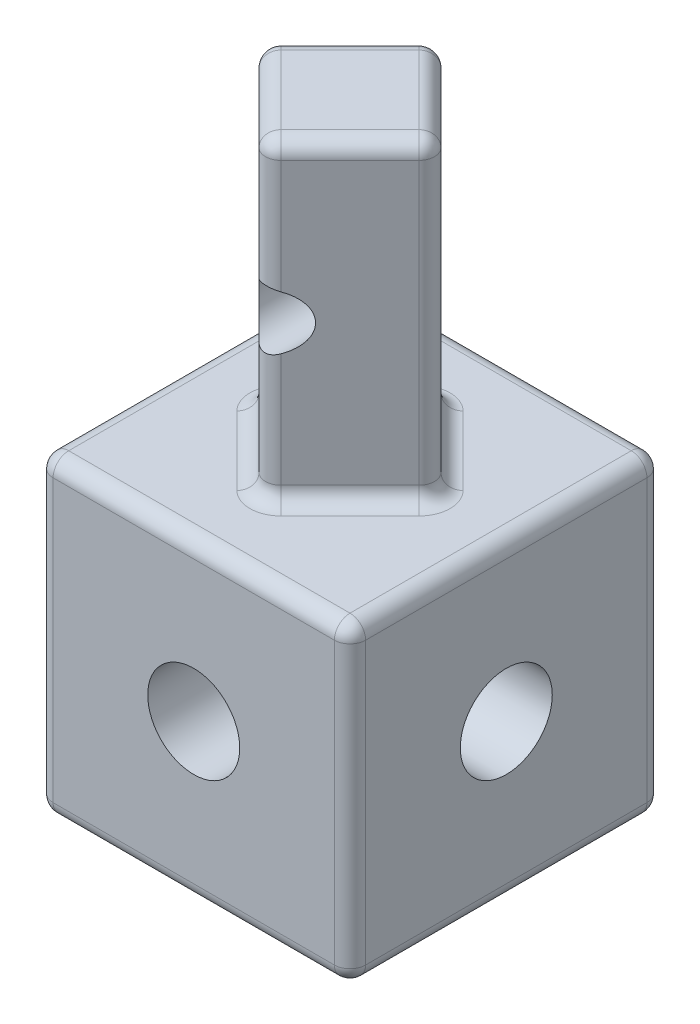
SolidWorks part; units mm, degrees
ref_plane "Front Plane" through (0, 0, 0) normal (0, 0, 1) x (1, 0, 0)
ref_plane "Top Plane" through (0, 0, 0) normal (0, 1, 0) x (1, 0, 0)
ref_plane "Right Plane" through (0, 0, 0) normal (1, 0, 0) x (0, 0, -1)
sketch "Sketch1" plane through (0, 0, 0) normal (0, 1, 0) x (1, 0, 0)
  line L1 (0, 0) -> (17, 0)
  line L2 (0, 0) -> (0, -17)
  line L3 (0, -17) -> (17, -17)
  line L4 (17, 0) -> (17, -17)
  dimension "D1" = 17
extrude "Boss-Extrude1" add sketch "Sketch1" along normal blind 17
sketch "Sketch2" plane through (0, 17, 0) normal (0, 1, 0) x (1, 0, 0)
  line L0 (0, 0) -> (17, -17) construction
  line L2 (3.5503, -8.5) -> (8.5, -3.5503)
  line L3 (3.5503, -8.5) -> (8.5, -13.4497)
  line L4 (8.5, -13.4497) -> (13.4497, -8.5)
  line L5 (8.5, -3.5503) -> (13.4497, -8.5)
  line L6 (3.5503, -8.5) -> (13.4497, -8.5) construction
  line L7 (8.5, -13.4497) -> (8.5, -3.5503) construction
  point P4 (8.5, -8.5)
  dimension "D1" = 7
  dimension "D2" = 90
extrude "Boss-Extrude2" add sketch "Sketch2" along normal blind 17
sketch3d "3DSketch7"
  line L0 (13.4497, 34, 8.5) -> (13.4497, 17, 8.5) construction
  circle A0 centre (8.4384, 25.4985, 8.5) radius 1.6
  point P4 (8.4384, 25.4985, 10.1)
  dimension "D1" = 3.2
extrude "Cut-Extrude1" cut sketch "3DSketch7" along direction (0, 0, 1) on the side of the normal through all and the other way blind 18 contours A0
hole_wizard "CBORE for #00 Binding Head Machine Screw1" positions "Sketch6" profile "Sketch8" counterbore size "#00" standard "ANSI Inch"
sketch "Sketch6" plane through (0, 0, 17) normal (0, 0, 1) x (1, 0, 0)
  point P0 (8.5, 8.5)
sketch "Sketch8" plane through (8.5, 8.5, 17) normal (1, 0, 0) x (0, -1, 0)
  line L0 (0, 0) -> (0, 10.9157)
  line L1 (0, 10.9157) -> (1.524, 10)
  line L2 (1.524, 10) -> (1.524, 5.4004)
  line L3 (1.524, 5.4004) -> (2.159, 4.0386)
  line L4 (2.159, 4.0386) -> (2.5019, 4.0386)
  line L5 (2.5019, 4.0386) -> (2.5019, 0)
  line L6 (2.5019, 0) -> (0, 0)
  line L9 (-1.524, 5.4004) -> (-2.159, 4.0386) construction
  line L10 (0, 10.9157) -> (-1.524, 10) construction
  line L11 (0, -6.35) -> (0, 107.95) construction
  dimension "Hole Dia." = 3.048
  dimension "Hole Depth" = 10
  dimension "C'Bore Dia." = 5.0038
  dimension "C'Bore Depth" = 4.0386
  dimension "Mid C'Sink Dia." = 4.318
  dimension "Mid C'Sink Angle" = 50
  dimension "Drill Angle" = 118
hole_wizard "CBORE for #00 Binding Head Machine Screw2" positions "Sketch9" profile "Sketch10" counterbore size "#00" standard "ANSI Inch"
sketch "Sketch9" plane through (17, 0, 0) normal (1, 0, 0) x (0, 0, -1)
  point P0 (-8.5, 8.5)
sketch "Sketch10" plane through (17, 8.5, 8.5) normal (0, 1, 0) x (0, 0, -1)
  line L0 (0, 0) -> (0, 10)
  line L1 (0, 10) -> (1.524, 10)
  line L2 (1.524, 10) -> (1.524, 5.4004)
  line L3 (1.524, 5.4004) -> (2.159, 4.0386)
  line L4 (2.159, 4.0386) -> (2.5019, 4.0386)
  line L5 (2.5019, 4.0386) -> (2.5019, 0)
  line L6 (2.5019, 0) -> (0, 0)
  line L9 (-1.524, 5.4004) -> (-2.159, 4.0386) construction
  line L10 (0, 10) -> (-1.524, 10) construction
  line L11 (0, -6.35) -> (0, 107.95) construction
  dimension "Hole Dia." = 3.048
  dimension "Hole Depth" = 10
  dimension "C'Bore Dia." = 5.0038
  dimension "C'Bore Depth" = 4.0386
  dimension "Mid C'Sink Dia." = 4.318
  dimension "Mid C'Sink Angle" = 50
  dimension "Drill Angle" = 180
hole_wizard "CBORE for #00 Binding Head Machine Screw3" positions "Sketch11" profile "Sketch12" counterbore size "#00" standard "ANSI Inch"
sketch "Sketch11" plane through (0, 0, 0) normal (0, 0, -1) x (-1, 0, 0)
  point P0 (-8.5, 8.5)
sketch "Sketch12" plane through (8.5, 8.5, 0) normal (1, 0, 0) x (0, 1, 0)
  line L0 (0, 0) -> (0, 10)
  line L1 (0, 10) -> (1.524, 10)
  line L2 (1.524, 10) -> (1.524, 5.4004)
  line L3 (1.524, 5.4004) -> (2.159, 4.0386)
  line L4 (2.159, 4.0386) -> (2.5019, 4.0386)
  line L5 (2.5019, 4.0386) -> (2.5019, 0)
  line L6 (2.5019, 0) -> (0, 0)
  line L9 (-1.524, 5.4004) -> (-2.159, 4.0386) construction
  line L10 (0, 10) -> (-1.524, 10) construction
  line L11 (0, -6.35) -> (0, 107.95) construction
  dimension "Hole Dia." = 3.048
  dimension "Hole Depth" = 10
  dimension "C'Bore Dia." = 5.0038
  dimension "C'Bore Depth" = 4.0386
  dimension "Mid C'Sink Dia." = 4.318
  dimension "Mid C'Sink Angle" = 50
  dimension "Drill Angle" = 180
hole_wizard "CBORE for #00 Binding Head Machine Screw4" positions "Sketch13" profile "Sketch14" counterbore size "#00" standard "ANSI Inch"
sketch "Sketch13" plane through (0, 0, 0) normal (-1, 0, 0) x (0, 0, 1)
  line L0 (0, 8.5) -> (17, 8.5)
  line L1 (0, 17) -> (0, 0) construction
  line L2 (17, 17) -> (17, 0) construction
  point P9 (8.5, 8.5)
sketch "Sketch14" plane through (0, 8.5, 8.5) normal (0, 1, 0) x (0, 0, 1)
  line L0 (0, 0) -> (0, 10)
  line L1 (0, 10) -> (1.524, 10)
  line L2 (1.524, 10) -> (1.524, 5.4004)
  line L3 (1.524, 5.4004) -> (2.159, 4.0386)
  line L4 (2.159, 4.0386) -> (2.5019, 4.0386)
  line L5 (2.5019, 4.0386) -> (2.5019, 0)
  line L6 (2.5019, 0) -> (0, 0)
  line L9 (-1.524, 5.4004) -> (-2.159, 4.0386) construction
  line L10 (0, 10) -> (-1.524, 10) construction
  line L11 (0, -6.35) -> (0, 107.95) construction
  dimension "Hole Dia." = 3.048
  dimension "Hole Depth" = 10
  dimension "C'Bore Dia." = 5.0038
  dimension "C'Bore Depth" = 4.0386
  dimension "Mid C'Sink Dia." = 4.318
  dimension "Mid C'Sink Angle" = 50
  dimension "Drill Angle" = 180
sketch "Sketch17" plane through (0, 0, 0) normal (0, -1, 0) x (1, 0, 0)
  line L0 (0, 17) -> (17, 0)
  line L1 (17, 0) -> (17, 17)
  line L2 (17, 17) -> (0, 0)
  point P10 (8.5, 8.5)
hole_wizard "CBORE for #0 Binding Head Machine Screw1" positions "Sketch17" profile "Sketch18" counterbore size "#0" standard "ANSI Inch"
sketch "Sketch18" plane through (8.5, 0, 8.5) normal (1, 0, 0) x (0, 0, -1)
  line L0 (0, 0) -> (0, 18.5875)
  line L1 (0, 18.5875) -> (1.5875, 17)
  line L2 (1.5875, 17) -> (1.5875, 5.1072)
  line L3 (1.5875, 5.1072) -> (1.6002, 5.08)
  line L4 (1.6002, 5.08) -> (2.5019, 5.08)
  line L5 (2.5019, 5.08) -> (2.5019, 0)
  line L6 (2.5019, 0) -> (0, 0)
  line L9 (-1.5875, 5.1072) -> (-1.6002, 5.08) construction
  line L10 (0, 18.5875) -> (-1.5875, 17) construction
  line L11 (0, -6.35) -> (0, 107.95) construction
  dimension "Hole Dia." = 3.175
  dimension "Hole Depth" = 17
  dimension "C'Bore Dia." = 5.0038
  dimension "C'Bore Depth" = 5.08
  dimension "Mid C'Sink Dia." = 3.2004
  dimension "Mid C'Sink Angle" = 50
  dimension "Drill Angle" = 90
fillet "Fillet4" radius 0.85 14 edges at (6.0251, 17, 10.9749) (6.0251, 17, 6.0251) (10.9749, 17, 10.9749) (8.5, 30.5486, 3.5503) (8.5, 20.4498, 3.5503) (8.5, 20.4498, 13.4497) (8.5, 30.5486, 13.4497) (10.9749, 17, 6.0251) (13.4497, 25.5, 8.5) (3.5503, 25.5, 8.5) (6.0251, 34, 10.9749) (10.9749, 34, 10.9749) (10.9749, 34, 6.0251) (6.0251, 34, 6.0251)
fillet "Fillet8" radius 0.85 3 edges at (17, 0, 8.5) (17, 8.5, 17) (17, 8.5, 0) type face fillet first side face at (17, 8.5, 5.9981) second side face at (5.9981, 8.5, 0) second side face at (0, 8.5, 11.0019) second side face at (8.5, 0, 8.5) second side face at (11.0019, 8.5, 17)
fillet "Fillet9" radius 0.85 3 edges at (8.075, 17, 17) (8.075, 17, 0) (0, 17, 8.5) type face fillet first side face at (5.9981, 8.5, 0) first side face at (0, 8.5, 11.0019) first side face at (8.075, 0, 8.5) first side face at (11.0019, 8.5, 17) second side face at (11.1087, 17, 8.5)
fillet "Fillet10" radius 0.85 9 edges at (0.249, 16.751, 0.249) (16.751, 0.249, 0.249) (0.249, 16.751, 16.751) (16.751, 0.249, 16.751) (0, 8.075, 0) (8.075, 0, 0) (0, 0, 8.5) (0, 8.075, 17) (8.075, 0, 17)
